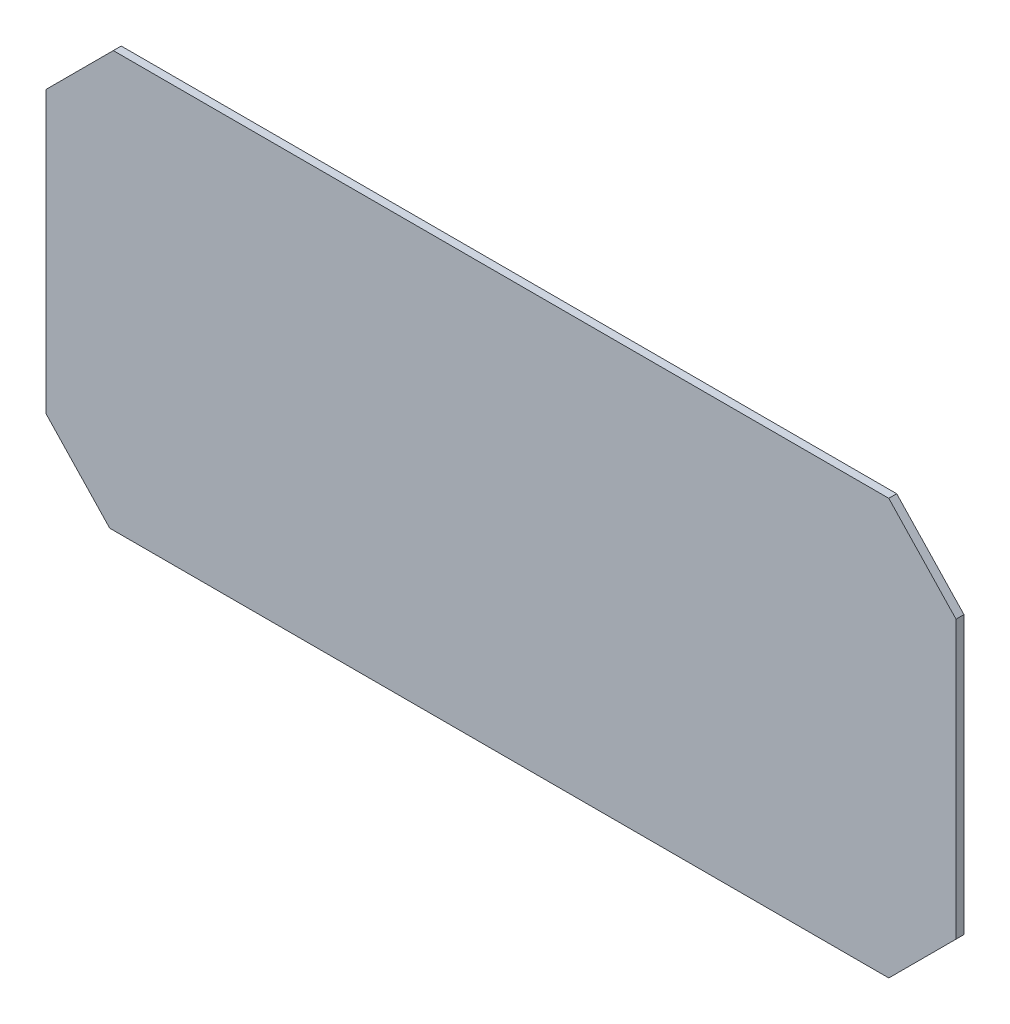
SolidWorks part; units mm, degrees
ref_plane "Plan de face" through (0, 0, 0) normal (0, 0, 1) x (1, 0, 0)
ref_plane "Plan de dessus" through (0, 0, 0) normal (0, 1, 0) x (1, 0, 0)
ref_plane "Plan de droite" through (0, 0, 0) normal (1, 0, 0) x (0, 0, -1)
sketch "Esquisse1" plane through (0, 0, 0) normal (0, 0, 1) x (1, 0, 0)
  line L1 (0, 0) -> (230, 0) construction
  line L2 (0, 0) -> (0, -105) construction
  line L3 (0, -105) -> (230, -105) construction
  line L4 (230, 0) -> (230, -105) construction
  line L8 (0, -17) -> (0, -88)
  line L9 (0, -88) -> (16.0933, -105)
  line L10 (16.0933, -105) -> (213, -105)
  line L11 (213, -105) -> (230, -88)
  line L12 (230, -88) -> (230, -17.9578)
  line L13 (230, -17.9578) -> (213, 0)
  line L14 (213, 0) -> (17, 0)
  line L15 (17, 0) -> (0, -17)
  dimension "D1" = 230
  dimension "D2" = 105
  dimension "D3" = 16.0933
  dimension "D4" = 17
  dimension "D5" = 17
  dimension "D6" = 17
  dimension "D7" = 17
  dimension "D8" = 17
  dimension "D9" = 17
extrude "Boss.-Extru.1" add sketch "Esquisse1" along normal blind 2
